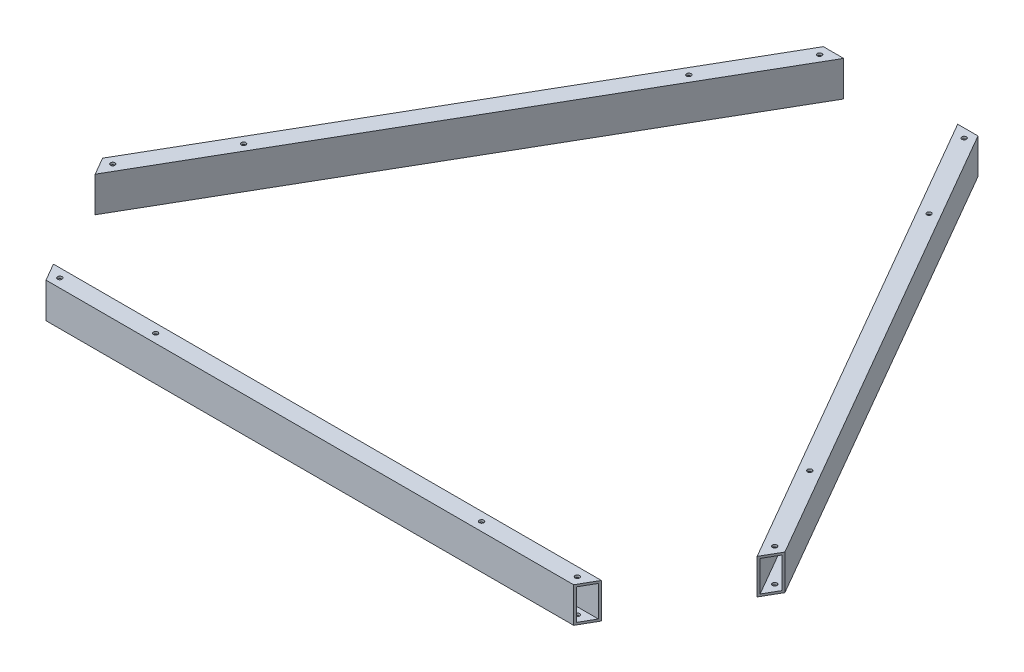
SolidWorks part; units mm, degrees
ref_plane "Front Plane" through (0, 0, 0) normal (0, 0, 1) x (1, 0, 0)
ref_plane "Top Plane" through (0, 0, 0) normal (0, 1, 0) x (1, 0, 0)
ref_plane "Right Plane" through (0, 0, 0) normal (1, 0, 0) x (0, 0, -1)
sketch "Sketch1" plane through (0, 0, 0) normal (0, 1, 0) x (1, 0, 0)
  line L0 (-9.297, 454.0294) -> (-569.6128, -516.4659)
  line L1 (-569.6128, -516.4659) -> (551.0187, -516.4659)
  line L2 (551.0187, -516.4659) -> (-9.297, 454.0294)
  line L3 (-120.952, 311.4374) -> (102.3579, 311.4374)
  line L4 (-204.7728, 166.2555) -> (186.1787, 166.2555)
  line L5 (-501.952, -348.4739) -> (-390.297, -541.8659)
  line L6 (-9.297, 504.8294) -> (-613.6069, -541.8659)
  line L7 (-613.6069, -541.8659) -> (595.0128, -541.8659)
  line L8 (595.0128, -541.8659) -> (-9.297, 504.8294)
  line L9 (-418.1311, -203.292) -> (-222.6554, -541.8659)
  line L10 (371.703, -541.8659) -> (483.3579, -348.4739)
  line L11 (204.0613, -541.8659) -> (399.537, -203.292)
  line L12 (-1.9647, 492.1294) -> (-598.9422, -541.8659) construction
  line L13 (-16.6294, 492.1294) -> (580.3481, -541.8659) construction
  line L14 (587.6804, -529.1659) -> (-606.2745, -529.1659) construction
  circle A0 centre (-113.6196, 298.7374) radius 3.2512
  circle A1 centre (-182.7757, 178.9555) radius 3.2512
  circle A2 centre (95.0255, 298.7374) radius 3.2512
  circle A3 centre (164.1816, 178.9555) radius 3.2512
  circle A4 centre (468.6932, -348.4739) radius 3.2512
  circle A5 centre (399.537, -228.692) radius 3.2512
  circle A6 centre (226.0584, -529.1659) radius 3.2512
  circle A7 centre (364.3706, -529.1659) radius 3.2512
  circle A8 centre (-382.9647, -529.1659) radius 3.2512
  circle A9 centre (-244.6524, -529.1659) radius 3.2512
  circle A10 centre (-487.2873, -348.4739) radius 3.2512
  circle A11 centre (-418.1311, -228.692) radius 3.2512
  dimension "D13" = 6.5024
  dimension "D14" = 6.5024
  dimension "D15" = 6.5024
  dimension "D16" = 6.5024
  dimension "D17" = 6.5024
  dimension "D18" = 6.5024
  dimension "D19" = 6.5024
  dimension "D20" = 6.5024
  dimension "D21" = 6.5024
  dimension "D22" = 6.5024
  dimension "D23" = 6.5024
  dimension "D24" = 6.5024
  dimension "D25" = 12.7
  dimension "D26" = 12.7
  dimension "D27" = 12.7
  dimension "D28" = 12.7
  dimension "D29" = 12.7
  dimension "D30" = 12.7
  dimension "D31" = 12.7
  dimension "D32" = 12.7
  dimension "D33" = 12.7
  dimension "D34" = 12.7
  dimension "D35" = 12.7
  dimension "D36" = 12.7
  dimension "D1" = 25.4
  dimension "D2" = 25.4
  dimension "D3" = 25.4
  dimension "D4" = 60
  dimension "D5" = 145.1819
  dimension "D6" = 390.9515
  dimension "D7" = 120
  dimension "D8" = 145.1819
  dimension "D9" = 390.9515
  dimension "D10" = 145.1819
  dimension "D11" = 390.9515
  dimension "D12" = 762
extrude "Boss-Extrude1" add sketch "Sketch1" along normal blind 50.8 contours L6 L9 L0 L4 | L9 L6 L5 L0 A11 A10 | L9 L1 L5 L7 A9 A8 | L7 L11 L1 L9 | L11 L7 L10 L1 A7 A6 | L11 L2 L10 L8 A5 A4 | L2 L11 L8 L4 | L4 L8 L3 L2 A3 A2 | L3 L6 L4 L0 A1 A0 region at (-148.1977, 0, -238.8465) region at (129.6036, 0, -238.8465) region at (-300.3316, 0, 24.9386) region at (281.7375, 0, 24.9386) region at (-452.7092, 0, 288.583) region at (434.1151, 0, 288.583) region at (-313.8086, 0, 529.1659) region at (-9.297, 0, 529.0253) region at (295.2145, 0, 529.1659)
sketch "Sketch2" plane through (513.412, 0, 296.4186) normal (0.866, 0, 0.5) x (0.5, 0, -0.866)
  line L0 (-283.4182, 50.8) -> (-254.0888, 50.8) construction
  line L1 (-280.2432, 47.625) -> (-257.2638, 47.625)
  line L2 (-280.2432, 47.625) -> (-280.2432, 3.175)
  line L3 (-280.2432, 3.175) -> (-257.2638, 3.175)
  line L4 (-257.2638, 47.625) -> (-257.2638, 3.175)
  line L5 (-283.4182, 50.8) -> (-283.4182, 0) construction
  line L6 (-254.0888, 50.8) -> (-254.0888, 0) construction
  line L7 (-283.4182, 0) -> (-254.0888, 0) construction
  dimension "D1" = 3.175
  dimension "D2" = 3.175
  dimension "D3" = 3.175
  dimension "D4" = 3.175
extrude "Cut-Extrude1" cut sketch "Sketch2" along direction (1, 0, 0) on the side against the normal through all
sketch "Sketch3" plane through (-527.3576, 0, 304.4701) normal (-0.866, 0, 0.5) x (0.5, 0, 0.866)
  line L0 (50.8113, 50.8) -> (80.1407, 50.8) construction
  line L1 (53.9863, 47.625) -> (76.9657, 47.625)
  line L2 (53.9863, 47.625) -> (53.9863, 3.175)
  line L3 (53.9863, 3.175) -> (76.9657, 3.175)
  line L4 (76.9657, 47.625) -> (76.9657, 3.175)
  line L5 (50.8113, 50.8) -> (50.8113, 0) construction
  line L6 (80.1407, 50.8) -> (80.1407, 0) construction
  line L7 (50.8113, 0) -> (80.1407, 0) construction
  dimension "D1" = 3.175
  dimension "D2" = 3.175
  dimension "D3" = 3.175
  dimension "D4" = 3.175
extrude "Cut-Extrude2" cut sketch "Sketch3" along direction (-0.5, 0, 0.866) on the side against the normal through all
sketch "Sketch4" plane through (513.412, 0, 296.4186) normal (0.866, 0, 0.5) x (0.5, 0, -0.866)
  line L0 (-89.4377, 50.8) -> (-60.1084, 50.8) construction
  line L1 (-86.2627, 47.625) -> (-63.2834, 47.625)
  line L2 (-86.2627, 47.625) -> (-86.2627, 3.175)
  line L3 (-86.2627, 3.175) -> (-63.2834, 3.175)
  line L4 (-63.2834, 47.625) -> (-63.2834, 3.175)
  line L5 (-89.4377, 0) -> (-60.1084, 0) construction
  line L6 (-60.1084, 50.8) -> (-60.1084, 0) construction
  line L7 (-89.4377, 50.8) -> (-89.4377, 0) construction
  dimension "D1" = 3.175
  dimension "D2" = 3.175
  dimension "D3" = 3.175
  dimension "D4" = 3.175
extrude "Cut-Extrude3" cut sketch "Sketch4" along direction (-0.5, 0, -0.866) on the side against the normal through all
